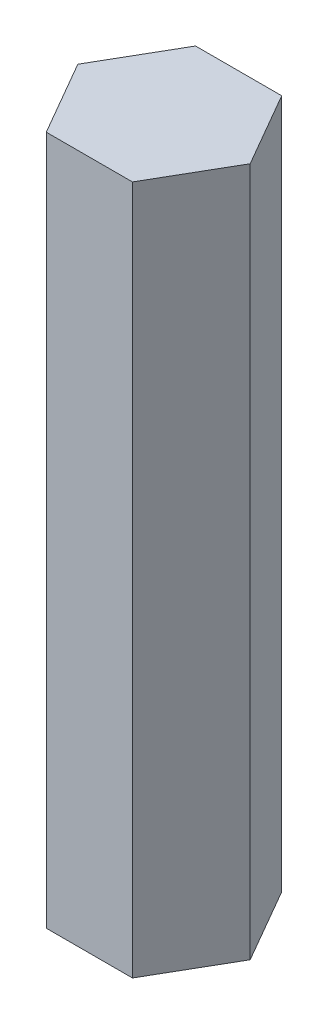
SolidWorks part; units mm, degrees
ref_plane "Front Plane" through (0, 0, 0) normal (0, 0, 1) x (1, 0, 0)
ref_plane "Top Plane" through (0, 0, 0) normal (0, 1, 0) x (1, 0, 0)
ref_plane "Right Plane" through (0, 0, 0) normal (1, 0, 0) x (0, 0, -1)
sketch "Esquisse3" plane through (0, 0, 0) normal (0, 1, 0) x (1, 0, 0)
  line L1 (3, 0) -> (1.5, 2.5981)
  line L2 (1.5, 2.5981) -> (-1.5, 2.5981)
  line L3 (-1.5, 2.5981) -> (-3, 0)
  line L4 (-3, 0) -> (-1.5, -2.5981)
  line L5 (-1.5, -2.5981) -> (1.5, -2.5981)
  line L6 (1.5, -2.5981) -> (3, 0)
  circle A0 centre (0, 0) radius 2.5981 construction
  dimension "D1" = 3
  dimension "D2" = 1.5
extrude "Boss.-Extru.1" add sketch "Esquisse3" along normal blind 24 contours L2 L3 L4 L5 L6 L1
ref_plane "Plan1" through (0, 0, 0) normal (0, 0, 1) x (1, 0, 0)
ref_point "Point1"
ref_axis "Axe1" through (0, 0, 0) along (0, 1, 0)
